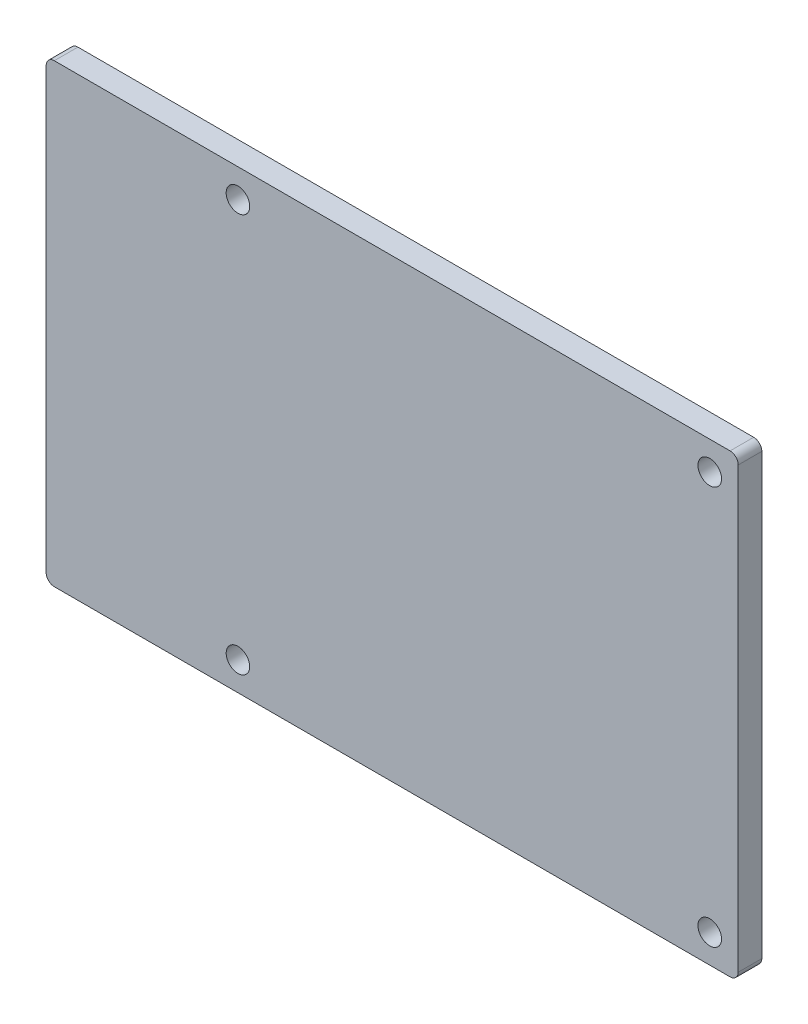
SolidWorks part; units mm, degrees
ref_plane "Front Plane" through (0, 0, 0) normal (0, 0, 1) x (1, 0, 0)
ref_plane "Top Plane" through (0, 0, 0) normal (0, 1, 0) x (1, 0, 0)
ref_plane "Right Plane" through (0, 0, 0) normal (1, 0, 0) x (0, 0, -1)
sketch "Sketch1" plane through (0, 0, 0) normal (0, 0, 1) x (1, 0, 0)
  line L4 (0, -47.5) -> (0, 75.1224) construction
  line L5 (-53.5, -47.5) -> (53.5, -47.5) construction
  line L6 (-53.5, -47.5) -> (-53.5, 47.5) construction
  line L7 (-53.5, 47.5) -> (-45.802, 47.5) construction
  line L8 (53.5, -47.5) -> (53.5, 47.5) construction
  line L9 (-53.5, -47.5) -> (53.5, 47.5) construction
  line L10 (-53.5, 47.5) -> (53.5, -47.5) construction
  line L11 (0, 0) -> (92.3064, 0) construction
  line L12 (48, 57.5289) -> (48, -67.5733) construction
  line L13 (-48, 56.5105) -> (-48, -72.884) construction
  line L14 (-42, -16.4523) -> (43, -16.4523) construction
  line L15 (39.5367, -54.9766) -> (39.5367, 8.0477) construction
  line L16 (43.0367, 11.5477) -> (-42.0367, 11.5477) construction
  line L17 (43.0367, 11.5477) -> (43.0367, -44.4523) construction
  line L18 (43.0367, -44.4523) -> (-42.0367, -44.4523) construction
  line L19 (-42.0367, 11.5477) -> (-42.0367, -44.4523) construction
  line L20 (43.0367, 11.5477) -> (-42.0367, -44.4523) construction
  line L21 (43.0367, -44.4523) -> (-42.0367, 11.5477) construction
  line L22 (39.5367, -40.9523) -> (-18.4633, -40.9523) construction
  line L23 (39.5367, 8.0477) -> (-18.4633, 8.0477) construction
  line L24 (45.802, 47.5) -> (53.5, 47.5) construction
  line L26 (45.802, 47.5) -> (45.802, 62.5) construction
  line L27 (45.802, 62.5) -> (-45.802, 62.5) construction
  line L28 (-45.802, 47.5) -> (-45.802, 62.5) construction
  line L29 (45.802, 16.5583) -> (-45.802, 62.5) construction
  line L30 (45.802, 62.5) -> (-45.802, 16.5583) construction
  line L32 (43.0367, 11.5477) -> (-42.0367, 11.5477)
  line L33 (43.0367, 11.5477) -> (43.0367, -44.4523)
  line L34 (43.0367, -44.4523) -> (-42.0367, -44.4523)
  line L35 (-42.0367, 11.5477) -> (-42.0367, -44.4523)
  circle A0 centre (39.5367, -40.9523) radius 1.45 construction
  circle A1 centre (39.5367, 8.0477) radius 1.45 construction
  circle A2 centre (-18.4633, -40.9523) radius 1.45 construction
  circle A3 centre (-18.4633, 8.0477) radius 1.45 construction
  circle A4 centre (39.5367, 8.0477) radius 1.45
  circle A5 centre (39.5367, -40.9523) radius 1.45
  circle A6 centre (-18.4633, 8.0477) radius 1.45
  circle A7 centre (-18.4633, -40.9523) radius 1.4444
  point P0 (0, 0)
  point P12 (0.5, -16.4523)
  point P15 (0.5, -16.4523)
  point P31 (0, -47.5)
  point P32 (0, 39.5291)
  dimension "D3" = 5.5
  dimension "D10" = 2.9
  dimension "D11" = 2.9
  dimension "D13" = 2.9
  dimension "D14" = 2.9
  dimension "D1" = 107
  dimension "D2" = 95
  dimension "D4" = 5.5
  dimension "D5" = 85
  dimension "D6" = 56
  dimension "D7" = 3.5
  dimension "D8" = 3.5
  dimension "D9" = 49
  dimension "D12" = 58
  dimension "D15" = 58
  dimension "D16" = 0.5
  dimension "D17" = 15
extrude "Boss-Extrude2" add sketch "Sketch1" along normal blind 2.9
fillet "Fillet1" radius 1 4 edges at (-42.0367, 11.5477, 1.45) (43.0367, 11.5477, 1.45) (-42.0367, -44.4523, 1.45) (43.0367, -44.4523, 1.45)
